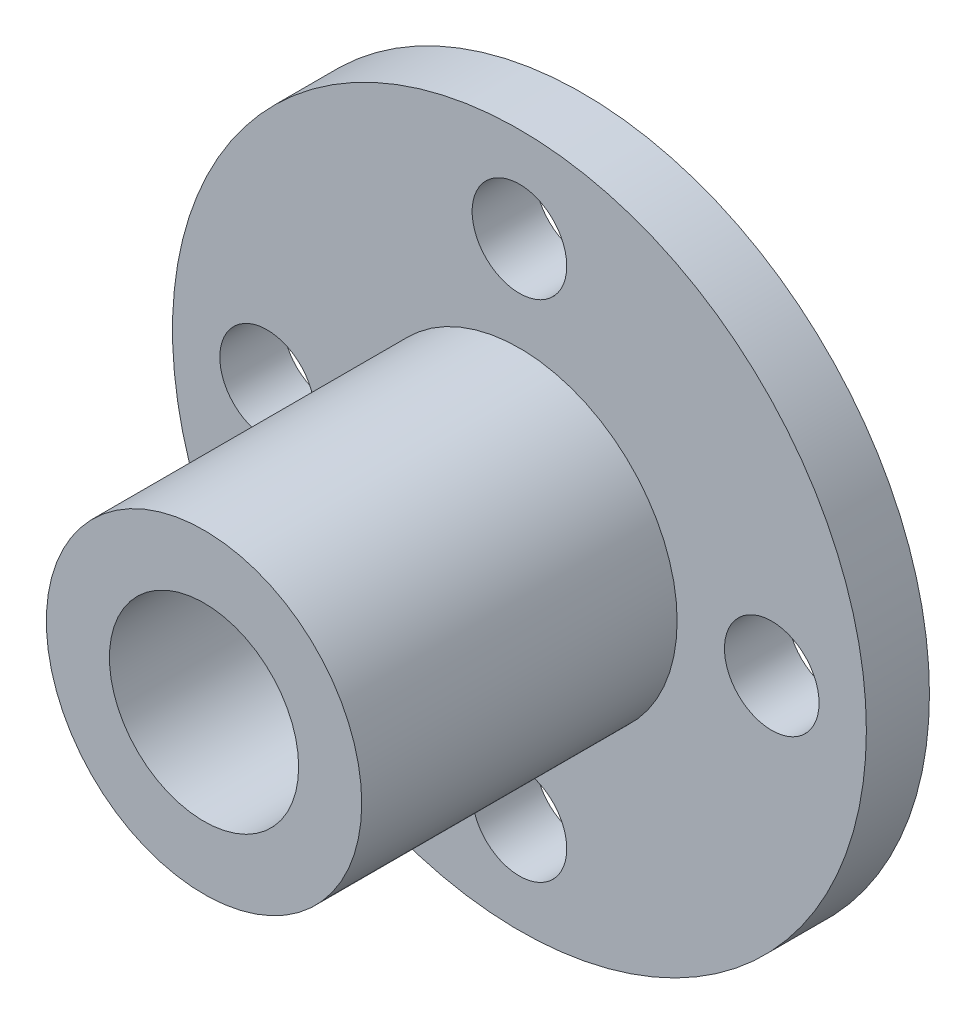
SolidWorks part; units mm, degrees
ref_plane "정면" through (0, 0, 0) normal (0, 0, 1) x (1, 0, 0)
ref_plane "윗면" through (0, 0, 0) normal (0, 1, 0) x (1, 0, 0)
ref_plane "우측면" through (0, 0, 0) normal (1, 0, 0) x (0, 0, -1)
sketch "스케치1" plane through (0, 0, 0) normal (0, 0, 1) x (1, 0, 0)
  circle A0 centre (0, 0) radius 11
  circle A1 centre (0, 8) radius 1.5
  circle A2 centre (8, 0) radius 1.5
  circle A3 centre (0, -8) radius 1.5
  circle A4 centre (-8, 0) radius 1.5
  point P14 (0, 0)
  dimension "D1" = 22
  dimension "D2" = 3
  dimension "D3" = 8
  dimension "D4" = 4
extrude "보스-돌출1" add sketch "스케치1" along normal blind 2
sketch "스케치2" plane through (0, 0, 2) normal (0, 0, 1) x (1, 0, 0)
  circle A0 centre (0, 0) radius 5
  circle A1 centre (0, 0) radius 3
  dimension "D1" = 6
  dimension "D2" = 10
extrude "보스-돌출2" add sketch "스케치2" along normal blind 10
extrude "컷-돌출1" cut sketch "스케치2<2>" against normal through all contours A1
sketch "스케치2<2>" plane through (0, 0, 2) normal (0, 0, 1) x (1, 0, 0) same geometry as "스케치2"
